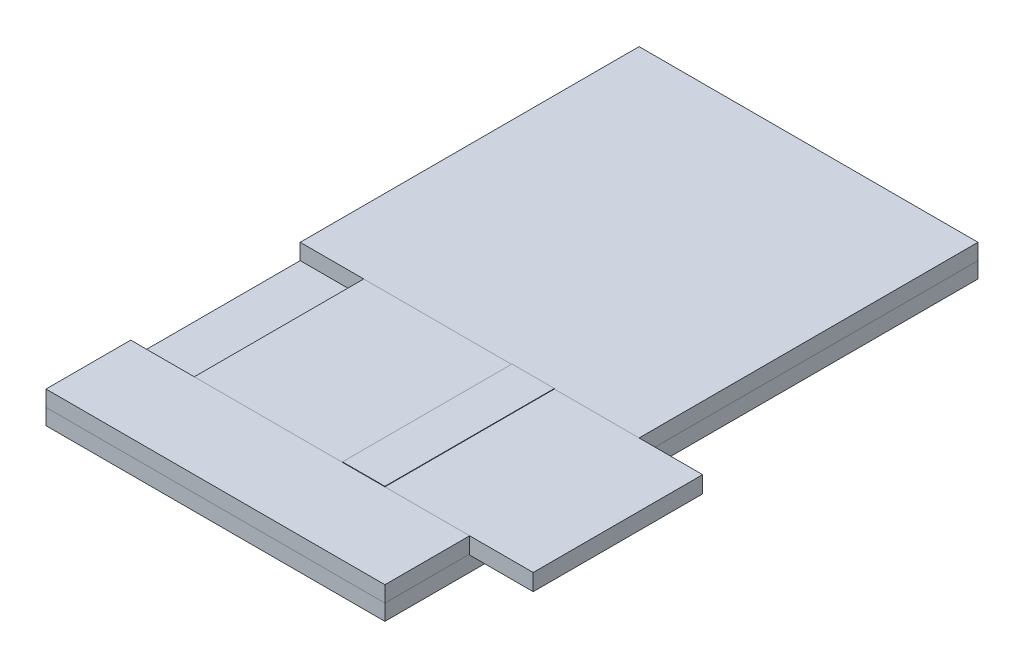
SolidWorks part; units mm, degrees
ref_plane "Front" through (0, 0, 0) normal (0, 0, 1) x (1, 0, 0)
ref_plane "Top" through (0, 0, 0) normal (0, 1, 0) x (1, 0, 0)
ref_plane "Right" through (0, 0, 0) normal (1, 0, 0) x (0, 0, -1)
ref_axis "X" through (-80.9, 0, 0) along (1, 0, 0)
ref_axis "Y" through (0, -50, 0) along (0, 1, 0)
ref_axis "Z" through (0, 0, -80.9) along (0, 0, 1)
sketch "Sketch1" plane through (0, 0, 0) normal (1, 0, 0) x (0, 0, -1)
  line L0 (-177.8, 0) -> (177.8, 0)
  line L1 (-177.8, 0) -> (-177.8, 9.525)
  line L2 (-177.8, 9.525) -> (177.8, 9.525)
  line L3 (177.8, 9.525) -> (177.8, 0)
  line L4 (177.8, 9.525) -> (-25.4, 9.525)
  line L5 (-25.4, 9.525) -> (-25.4, 19.05)
  line L6 (-25.4, 19.05) -> (177.8, 19.05)
  line L7 (177.8, 19.05) -> (177.8, 9.525)
  line L8 (-177.8, 9.525) -> (-177.8, 19.05)
  line L9 (-177.8, 19.05) -> (-127, 19.05)
  line L10 (-127, 19.05) -> (-127, 9.525)
  line L11 (-127, 9.525) -> (-177.8, 9.525)
  line L13 (-127, 19.05) -> (-25.4, 19.05)
  line L14 (-127, 19.05) -> (-127, 9.525)
  line L15 (-127, 9.525) -> (-25.4, 9.525)
  line L16 (-25.4, 19.05) -> (-25.4, 9.525)
  dimension "D1" = 355.6
  dimension "D2" = 9.525
  dimension "D3" = 9.525
  dimension "D4" = 203.2
  dimension "D6" = 50.8
extrude "Boss-Extrude1" add sketch "Sketch1" along normal mid plane 203.2 contours L3 L2 L1 L0 region at (0, 4.7625, 0)
extrude "Boss-Extrude2" add sketch "Sketch1<3>" along normal mid plane 203.2 separate body contours L4 L5 L6 L7
sketch "Sketch1<3>" plane through (0, 0, 0) normal (1, 0, 0) x (0, 0, -1) same geometry as "Sketch1"
extrude "Boss-Extrude3" add sketch "Sketch1<4>" along normal mid plane 203.2 separate body contours L8 L9 L10 L11
sketch "Sketch1<4>" plane through (0, 0, 0) normal (1, 0, 0) x (0, 0, -1) same geometry as "Sketch1"
extrude "Extrude-Thin1" add sketch "Sketch1<5>" along normal mid plane 203.2 from offset 38.1 separate body thin contours L13 thin type one direction wall 10
sketch "Sketch1<5>" plane through (0, 0, 0) normal (1, 0, 0) x (0, 0, -1) same geometry as "Sketch1"
sketch "Sketch2" plane through (0, 19.05, 0) normal (0, 1, 0) x (1, 0, 0)
  line L0 (50.8, -127) -> (50.8, -25.4)
  line L1 (139.7, -127) -> (-63.5, -127) construction
  line L2 (101.6, -25.4) -> (-101.6, -25.4) construction
  line L3 (50.8, -25.4) -> (25.4, -25.4)
  line L4 (25.4, -25.4) -> (25.4, -127)
  line L5 (25.4, -127) -> (50.8, -127)
  line L6 (38.1, -25.4) -> (38.1, -127) construction
  line L7 (139.7, -25.4) -> (-63.5, -25.4) construction
  dimension "D1" = 25.4
extrude "Boss-Extrude4" add sketch "Sketch2" along normal blind 0.3 separate body
